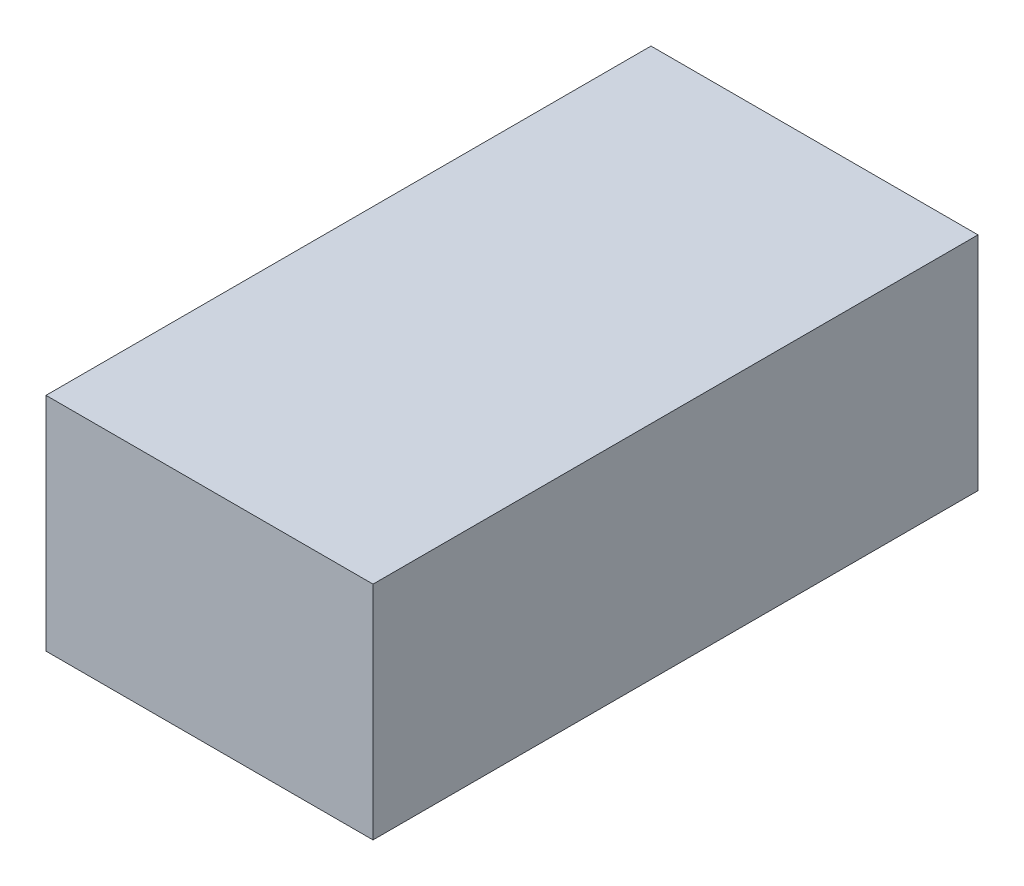
SolidWorks part; units mm, degrees
other "fluid_domain"
ref_plane "Front Plane" through (0, 0, 0) normal (0, 0, 1) x (1, 0, 0)
ref_plane "Top Plane" through (0, 0, 0) normal (0, 1, 0) x (1, 0, 0)
ref_plane "Right Plane" through (0, 0, 0) normal (1, 0, 0) x (0, 0, -1)
other "Configuration Table"
sketch "Sketch1" plane through (0, 0, 0) normal (1, 0, 0) x (0, 0, -1)
  line L1 (2500, -355) -> (-1200, -355)
  line L2 (2500, -355) -> (2500, 1000)
  line L3 (2500, 1000) -> (-1200, 1000)
  line L4 (-1200, -355) -> (-1200, 1000)
  line L5 (2500, -355) -> (-1200, 1000) construction
  line L6 (2500, 1000) -> (-1200, -355) construction
extrude "air_box" add sketch "Sketch1" along normal blind 2000 from offset 800 separate body offset against normal yes
sketch "Sketch2" plane through (0, 0, 0) normal (1, 0, 0) x (0, 0, -1)
  circle A0 centre (0, 0) radius 360
  circle A1 centre (0, 0) radius 200
extrude "wheel" add sketch "Sketch2" along normal blind 285 from offset 190 separate body offset against normal yes
sketch "Sketch3" plane through (0, 0, 0) normal (1, 0, 0) x (0, 0, -1)
  circle A0 centre (0, 0) radius 360
extrude "cover" add sketch "Sketch3" along normal blind 10 from offset 200 separate body offset against normal yes
sketch "Sketch4" plane through (0, 0, 0) normal (1, 0, 0) x (0, 0, -1)
  circle A0 centre (0, 0) radius 164
extrude "rotor" add sketch "Sketch4" along normal mid plane 32 separate body
sketch "Sketch5" plane through (0, 0, 0) normal (1, 0, 0) x (0, 0, -1)
  line L1 (32, 88) -> (-32, 88)
  line L2 (32, 88) -> (32, 192)
  line L3 (32, 192) -> (-32, 192)
  line L4 (-32, 88) -> (-32, 192)
  line L5 (32, 88) -> (-32, 192) construction
  line L6 (32, 192) -> (-32, 88) construction
extrude "throat_outer" add sketch "Sketch5" along normal blind 82 from offset 18 separate body
sketch "Sketch6" plane through (0, 0, 0) normal (1, 0, 0) x (0, 0, -1)
  line L1 (32, 88) -> (-300, 88)
  line L2 (32, 88) -> (32, 192)
  line L3 (32, 192) -> (-300, 192)
  line L4 (-300, 88) -> (-300, 192)
  line L5 (32, 88) -> (-300, 192) construction
  line L6 (32, 192) -> (-300, 88) construction
extrude "scoop_outer" add sketch "Sketch6" along normal blind 64 from offset 98 separate body
combine bodies "Combine1" operation type add bodies to combine 107 106
sketch "Sketch7" plane through (0, 0, 0) normal (1, 0, 0) x (0, 0, -1)
  line L1 (30, 90) -> (-30, 90)
  line L2 (30, 90) -> (30, 190)
  line L3 (30, 190) -> (-30, 190)
  line L4 (-30, 90) -> (-30, 190)
  line L5 (30, 90) -> (-30, 190) construction
  line L6 (30, 190) -> (-30, 90) construction
extrude "throat_inner" add sketch "Sketch7" along normal blind 91 from offset 10 separate body
sketch "Sketch8" plane through (0, 0, 0) normal (1, 0, 0) x (0, 0, -1)
  line L1 (30, 90) -> (-310, 90)
  line L2 (30, 90) -> (30, 190)
  line L3 (30, 190) -> (-310, 190)
  line L4 (-310, 90) -> (-310, 190)
  line L5 (30, 90) -> (-310, 190) construction
  line L6 (30, 190) -> (-310, 90) construction
extrude "scoop_inner" add sketch "Sketch8" along normal blind 60 from offset 100 separate body
combine bodies "Combine2" operation type subtract main body 108 bodies to subtract 109 110
sketch "Sketch9" plane through (0, 0, 0) normal (1, 0, 0) x (0, 0, -1)
  line L1 (28, 109) -> (-28, 109)
  line L2 (28, 109) -> (28, 111)
  line L3 (28, 111) -> (-28, 111)
  line L4 (-28, 109) -> (-28, 111)
  line L5 (28, 109) -> (-28, 111) construction
  line L6 (28, 111) -> (-28, 109) construction
extrude "louver1" add sketch "Sketch9" along normal blind 18 from offset 49 separate body
sketch "Sketch10" plane through (0, 0, 0) normal (1, 0, 0) x (0, 0, -1)
  line L1 (28, 129) -> (-28, 129)
  line L2 (28, 129) -> (28, 131)
  line L3 (28, 131) -> (-28, 131)
  line L4 (-28, 129) -> (-28, 131)
  line L5 (28, 129) -> (-28, 131) construction
  line L6 (28, 131) -> (-28, 129) construction
extrude "louver2" add sketch "Sketch10" along normal blind 18 from offset 49 separate body
sketch "Sketch11" plane through (0, 0, 0) normal (1, 0, 0) x (0, 0, -1)
  line L1 (28, 149) -> (-28, 149)
  line L2 (28, 149) -> (28, 151)
  line L3 (28, 151) -> (-28, 151)
  line L4 (-28, 149) -> (-28, 151)
  line L5 (28, 149) -> (-28, 151) construction
  line L6 (28, 151) -> (-28, 149) construction
extrude "louver3" add sketch "Sketch11" along normal blind 18 from offset 49 separate body
sketch "Sketch12" plane through (0, 0, 0) normal (1, 0, 0) x (0, 0, -1)
  line L1 (28, 169) -> (-28, 169)
  line L2 (28, 169) -> (28, 171)
  line L3 (28, 171) -> (-28, 171)
  line L4 (-28, 169) -> (-28, 171)
  line L5 (28, 169) -> (-28, 171) construction
  line L6 (28, 171) -> (-28, 169) construction
extrude "louver4" add sketch "Sketch12" along normal blind 18 from offset 49 separate body
combine bodies "Combine3" operation type subtract main body 102 bodies to subtract 103
combine bodies "Combine4" operation type subtract main body 116 bodies to subtract 104
combine bodies "Combine5" operation type subtract main body 117 bodies to subtract 105
combine bodies "Combine6" operation type subtract main body 118 bodies to subtract 111
combine bodies "Combine7" operation type subtract main body 119 bodies to subtract 112
combine bodies "Combine8" operation type subtract main body 120 bodies to subtract 113
combine bodies "Combine9" operation type subtract main body 121 bodies to subtract 114
combine bodies "Combine10" operation type subtract main body 122 bodies to subtract 115
